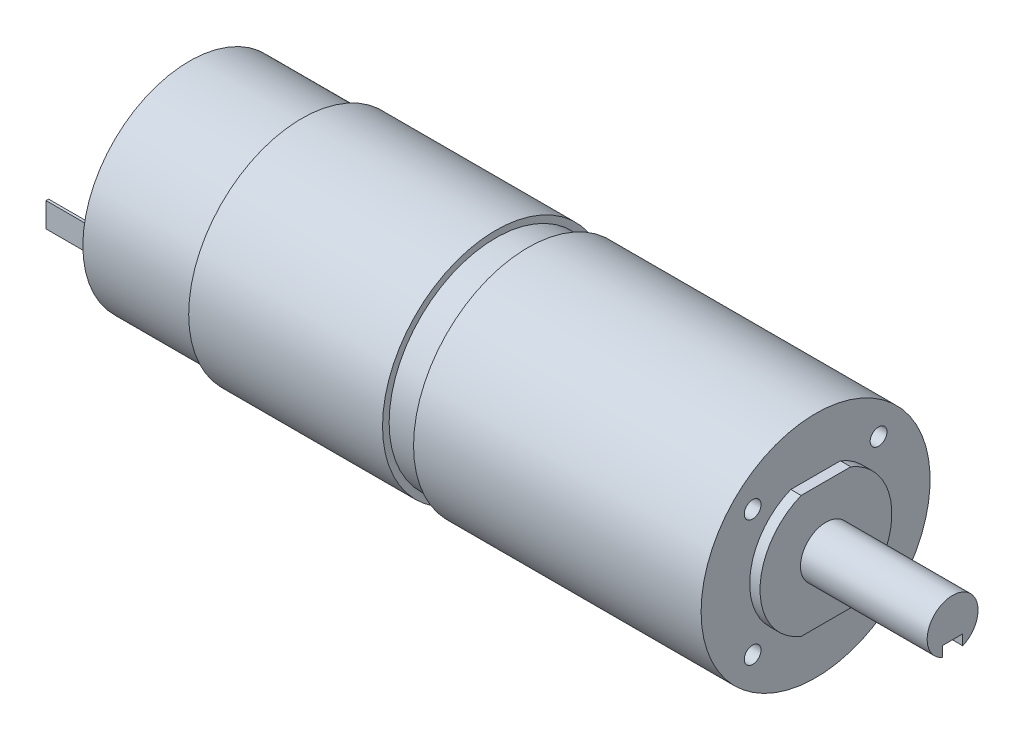
SolidWorks part; units mm, degrees
ref_plane "Front Plane" through (0, 0, 0) normal (0, 0, 1) x (1, 0, 0)
ref_plane "Top Plane" through (0, 0, 0) normal (0, 1, 0) x (1, 0, 0)
ref_plane "Right Plane" through (0, 0, 0) normal (1, 0, 0) x (0, 0, -1)
sketch "Sketch1" plane through (0, 0, 0) normal (0, 0, 1) x (1, 0, 0)
  line L0 (0, 0) -> (224.7846, 0) construction
  line L1 (0, 0) -> (0, 3.81)
  line L2 (0, 3.81) -> (5.08, 3.81)
  line L3 (5.08, 3.81) -> (5.08, 11.43)
  line L4 (5.08, 11.43) -> (9.017, 11.43)
  line L5 (9.017, 11.43) -> (9.017, 20.955)
  line L6 (9.017, 20.955) -> (31.115, 20.955)
  line L7 (31.115, 20.955) -> (31.115, 22.2504)
  line L8 (31.115, 22.2504) -> (69.215, 22.2504)
  line L9 (69.215, 22.2504) -> (69.215, 20.955)
  line L10 (69.215, 20.955) -> (75.565, 20.955)
  line L11 (75.565, 20.955) -> (75.565, 22.5044)
  line L12 (75.565, 22.5044) -> (132.08, 22.5044)
  line L13 (132.08, 22.5044) -> (132.08, 12.954)
  line L14 (132.08, 12.954) -> (134.112, 12.954)
  line L15 (134.112, 12.954) -> (134.112, 5)
  line L16 (134.112, 5) -> (159.004, 5)
  line L17 (159.004, 5) -> (159.004, 0)
  line L18 (0, 0) -> (159.004, 0)
  dimension "D1" = 159.004
  dimension "D2" = 66.548
  dimension "D3" = 56.515
  dimension "D4" = 2.032
  dimension "D5" = 26.924
  dimension "D6" = 10
  dimension "D7" = 25.908
  dimension "D8" = 44.5008
  dimension "D9" = 45.0088
  dimension "D10" = 5.08
  dimension "D11" = 7.62
  dimension "D12" = 22.86
  dimension "D13" = 41.91
  dimension "D14" = 38.1
  dimension "D15" = 6.35
revolve "Revolve1" add sketch "Sketch1" angle 360 about L0
sketch "Sketch2" plane through (159.004, 0, 0) normal (1, 0, 0) x (0, 0, -1)
  line L2 (-1.9939, -4.5852) -> (-1.9939, -2.5532)
  line L3 (-1.9939, -2.5532) -> (1.9939, -2.5532)
  line L4 (1.9939, -4.5852) -> (1.9939, -2.5532)
  circle A1 centre (0, 0) radius 5
  arc A2 (-1.9939, -4.5852) -> (1.9939, -4.5852) centre (0, 0) ccw
  point P0 (0, -2.5532)
  dimension "D2" = 3.9878
  dimension "D3" = 2.032
  dimension "D1" = 0
extrude "Cut-Extrude1" cut sketch "Sketch2" against normal blind 18.0086
sketch "Sketch3" plane through (134.112, 0, 0) normal (1, 0, 0) x (0, 0, -1)
  line L0 (-4.8755, 12.0015) -> (4.8755, 12.0015)
  line L1 (-4.8755, -12.0015) -> (4.8755, -12.0015)
  circle A0 centre (0, 0) radius 12.954 construction
  circle A1 centre (0, 0) radius 12.954
  arc A2 (-4.8755, -12.0015) -> (4.8755, -12.0015) centre (0, 0) ccw
  arc A3 (4.8755, 12.0015) -> (-4.8755, 12.0015) centre (0, 0) ccw
  dimension "D2" = 24.003
  dimension "D1" = 0
extrude "Cut-Extrude2" cut sketch "Sketch3" against normal up to surface (2.032 mm away) up to face at (132.08, 0, 22.5044)
hole_wizard "Tap Drill for M4x0.7 Tap2" positions "Sketch6" profile "Sketch4" hole size "M4x0.7" standard "ANSI Metric"
sketch "Sketch6" plane through (132.08, 0, 0) normal (1, 0, 0) x (0, 0, -1)
  line L0 (-12.3748, 12.3748) -> (12.3748, -12.3748) construction
  line L2 (12.3748, 12.3748) -> (-12.3748, -12.3748) construction
  line L4 (0, 17.5006) -> (0, -17.5006) construction
  circle A0 centre (0, 0) radius 17.5006 construction
  point P5 (-12.3748, 12.3748)
  point P6 (12.3748, -12.3748)
  point P9 (12.3748, 12.3748)
  point P10 (-12.3748, -12.3748)
  point P13 (0, 0)
  point P14 (0, 0)
  dimension "D1" = 35.0012
  dimension "D2" = 45
sketch "Sketch4" plane through (132.08, 12.3748, 12.3748) normal (0, 1, 0) x (0, 0, -1)
  line L0 (0, 0) -> (0, 12.7)
  line L1 (0, 12.7) -> (1.65, 12.7)
  line L2 (1.65, 12.7) -> (1.65, 0)
  line L5 (1.65, 0) -> (0, 0)
  line L10 (0, 12.7) -> (-1.65, 12.7) construction
  line L11 (0, -6.35) -> (0, 107.95) construction
  dimension "Hole Dia." = 3.3
  dimension "Hole Depth" = 12.7
  dimension "Drill Angle" = 180
ref_plane "Plane1" through (0, 0, 19.05) normal (0, 0, 1) x (1, 0, 0)
sketch "Sketch8" plane through (0, 0, 19.05) normal (0, 0, 1) x (1, 0, 0)
  line L0 (9.017, 11.43) -> (9.017, -11.43) construction
  line L1 (9.017, 2.413) -> (9.017, -2.413)
  line L2 (9.017, 2.413) -> (0.127, 2.413)
  line L3 (0.127, 2.413) -> (0.127, -2.413)
  line L4 (0.127, -2.413) -> (9.017, -2.413)
  point P6 (0.127, 0)
  dimension "D1" = 8.89
  dimension "D2" = 4.826
extrude "Boss-Extrude1" add sketch "Sketch8" against normal mid plane 0.508
mirror "Mirror1" about plane through (0, 0, 0) normal (0, 0, 1) of "Boss-Extrude1"
sketch "Sketch9" plane through (0.127, 0, 0) normal (-1, 0, 0) x (0, 0, 1)
  line L0 (-19.304, 2.413) -> (-18.796, -2.413) construction
  line L1 (-18.796, 2.413) -> (-19.304, -2.413) construction
  line L2 (18.796, 2.413) -> (19.304, -2.413) construction
  line L3 (19.304, 2.413) -> (18.796, -2.413) construction
  point P16 (19.05, 0)
  point P17 (-19.05, 0)
sketch "0_0_Point" plane through (0.127, 0, 0) normal (-1, 0, 0) x (0, 0, 1)
  point P0 (-19.05, 0)
other "0_0" parameters "Diameter"=2, "StubLength"=2
ref_axis "Axis1" through (-9.873, 0, -19.05) along (1, 0, 0)
sketch "0_1_Point" plane through (0.127, 0, 0) normal (-1, 0, 0) x (0, 0, 1)
  point P0 (19.05, 0)
other "0_1" parameters "Diameter"=2, "StubLength"=2
ref_axis "Axis2" through (-9.873, 0, 19.05) along (1, 0, 0)
